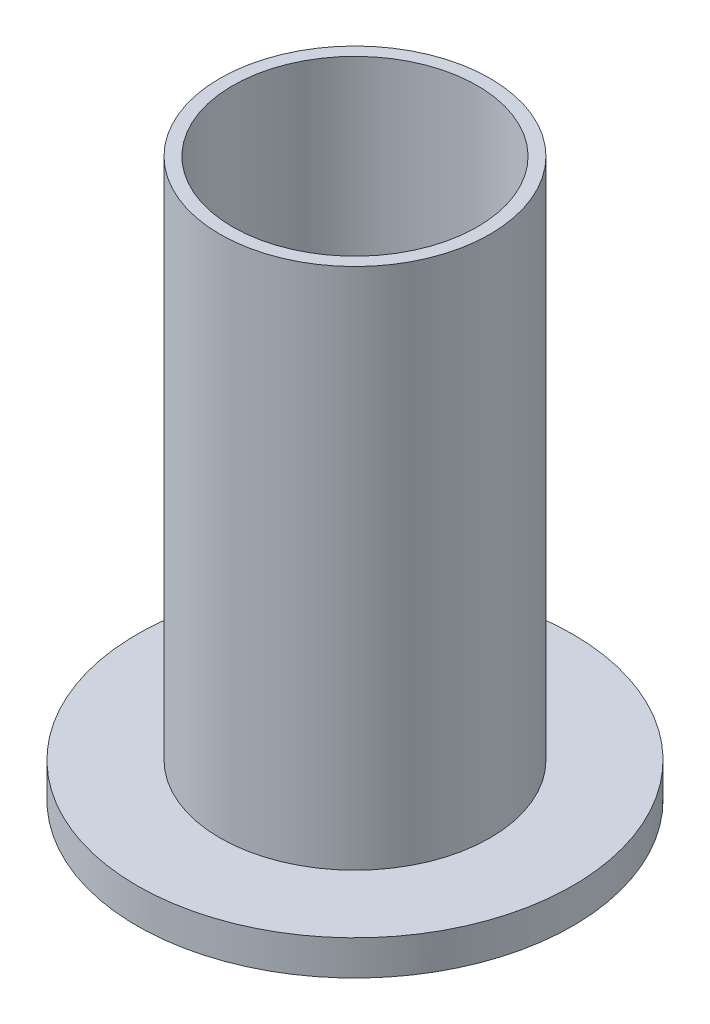
SolidWorks part; units mm, degrees
ref_plane "Front Plane" through (0, 0, 0) normal (0, 0, 1) x (1, 0, 0)
ref_plane "Top Plane" through (0, 0, 0) normal (0, 1, 0) x (1, 0, 0)
ref_plane "Right Plane" through (0, 0, 0) normal (1, 0, 0) x (0, 0, -1)
sketch "Sketch1" plane through (0, 0, 0) normal (0, 1, 0) x (1, 0, 0)
  line L1 (-50.8, -50.8) -> (50.8, -50.8)
  line L2 (-50.8, -50.8) -> (-50.8, 50.8)
  line L3 (-50.8, 50.8) -> (50.8, 50.8)
  line L4 (50.8, -50.8) -> (50.8, 50.8)
  line L5 (-50.8, -50.8) -> (50.8, 50.8) construction
  line L6 (-50.8, 50.8) -> (50.8, -50.8) construction
  point P0 (0, 0)
  dimension "D1" = 101.6
extrude "Boss-Extrude1" add sketch "Sketch1" along normal blind 10
sketch "Sketch2" plane through (0, 0, 0) normal (0, -1, 0) x (-1, 0, 0)
  circle A0 centre (0, 0) radius 5
  dimension "D1" = 10
extrude "Cut-Extrude1" cut sketch "Sketch2" against normal blind 5
sketch "Sketch3" plane through (0, 10, 0) normal (0, 1, 0) x (1, 0, 0)
  circle A0 centre (0, 0) radius 12.5
  dimension "D1" = 25
extrude "Boss-Extrude2" add sketch "Sketch3" along normal blind 2
sketch "Sketch4" plane through (0, 12, 0) normal (0, 1, 0) x (1, 0, 0)
  circle A0 centre (0, 0) radius 7.75
  dimension "D1" = 15.5
extrude "Boss-Extrude3" add sketch "Sketch4" along normal blind 30
sketch "Sketch6" plane through (0, 10, 0) normal (0, 1, 0) x (1, 0, 0)
  line L1 (50.8, 50.8) -> (-50.8, 50.8)
  line L2 (50.8, 50.8) -> (50.8, -50.8)
  line L3 (50.8, -50.8) -> (-50.8, -50.8)
  line L4 (-50.8, 50.8) -> (-50.8, -50.8)
extrude "Cut-Extrude2" cut sketch "Sketch6" against normal blind 10
sketch "Sketch7" plane through (0, 42, 0) normal (0, 1, 0) x (1, 0, 0)
  circle A0 centre (0, 0) radius 7.0239
  dimension "D1" = 14.0478
extrude "Cut-Extrude3" cut sketch "Sketch7" against normal blind 30
